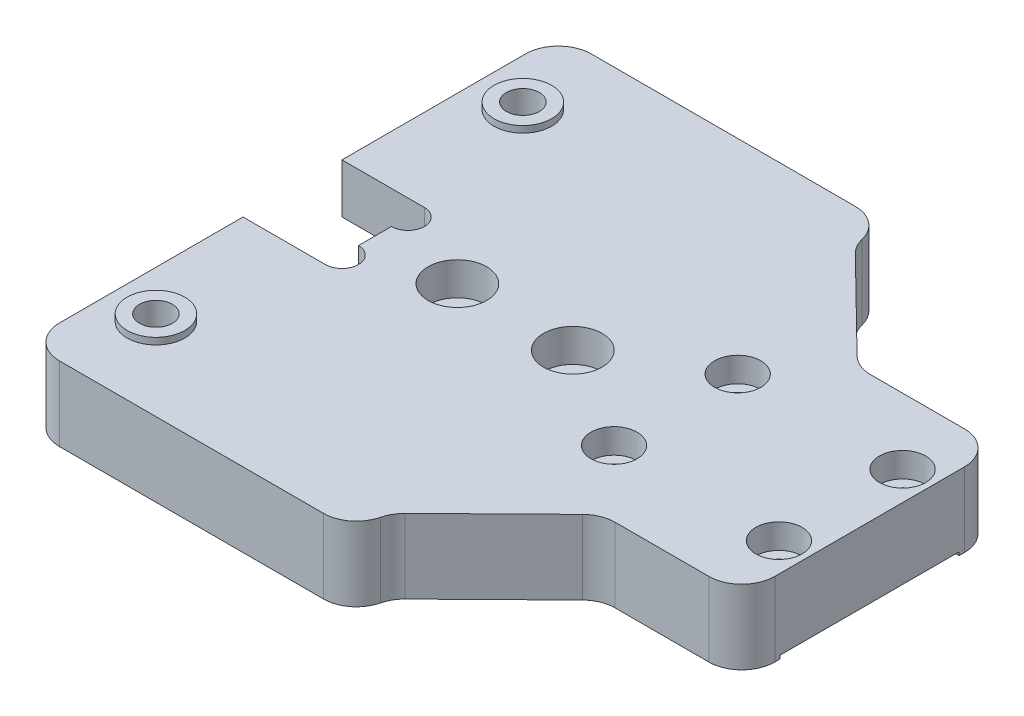
SolidWorks part; units mm, degrees
ref_plane "Front Plane" through (0, 0, 0) normal (0, 0, 1) x (1, 0, 0)
ref_plane "Top Plane" through (0, 0, 0) normal (0, 1, 0) x (1, 0, 0)
ref_plane "Right Plane" through (0, 0, 0) normal (1, 0, 0) x (0, 0, -1)
sketch "Sketch1" plane through (0, 0, 0) normal (0, 1, 0) x (1, 0, 0)
  line L0 (0, 0) -> (21.5, 0) construction
  line L5 (21.5, 20) -> (21.5, -20)
  line L6 (21.5, -20) -> (-20.5, -32.5)
  line L7 (-20.5, -32.5) -> (-84.5, -32.5)
  line L8 (-84.5, -32.5) -> (-84.5, 32.5)
  line L11 (-84.5, 32.5) -> (-20.5, 32.5)
  line L12 (-20.5, 32.5) -> (21.5, 20)
  circle A0 centre (0, 0) radius 12
  point P7 (21.5, 0)
  dimension "D4" = 24
  dimension "D6" = 9.5
  dimension "D1" = 40
  dimension "D2" = 106
  dimension "D3" = 65
  dimension "D5" = 64
extrude "Boss-Extrude1" add sketch "Sketch1" along normal mid plane 9
sketch "Sketch2" plane through (0, 4.5, 0) normal (0, 1, 0) x (1, 0, 0)
  line L0 (0, 0) -> (-19.5, 0) construction
  line L1 (-15.5, -15.5) -> (15.5, -15.5) construction
  line L2 (-15.5, -15.5) -> (-15.5, 15.5) construction
  line L3 (-15.5, 15.5) -> (15.5, 15.5) construction
  line L4 (15.5, -15.5) -> (15.5, 15.5) construction
  line L5 (-15.5, -15.5) -> (15.5, 15.5) construction
  line L6 (-15.5, 15.5) -> (15.5, -15.5) construction
  line L7 (-19.5, 27.5) -> (-19.5, -27.5) construction
  line L9 (-84.5, 32.5) -> (-84.5, -32.5) construction
  circle A0 centre (15.5, 15.5) radius 1.7
  circle A1 centre (-15.5, 15.5) radius 1.7
  circle A2 centre (-15.5, -15.5) radius 1.7
  circle A3 centre (15.5, -15.5) radius 1.7
  circle A4 centre (-19.5, 27.5) radius 1.7
  circle A5 centre (-19.5, -27.5) radius 1.7
  point P0 (0, 0)
  dimension "D2" = 3.4
  dimension "D1" = 31
  dimension "D3" = 55
  dimension "D4" = 65
extrude "Cut-Extrude1" cut sketch "Sketch2" against normal through all
fillet "Fillet1" radius 4 6 edges at (-84.5, 0, -32.5) (-84.5, 0, 32.5) (-20.5, 0, 32.5) (21.5, 0, 20) (-20.5, 0, -32.5) (21.5, 0, -20)
sketch "Sketch5" plane through (0, 4.5, 0) normal (0, 1, 0) x (1, 0, 0)
  line L0 (-24.5, 32.5) -> (-24.5, 10)
  line L1 (-21.0826, 32.5) -> (-80.5, 32.5) construction
  line L2 (-80.5, -32.5) -> (-21.0826, -32.5) construction
  line L3 (-84.5, 28.5) -> (-84.5, -28.5) construction
  line L4 (-24.5, 32.5) -> (26.912, 32.5)
  line L5 (-24.5, -10) -> (-29.5, -10) construction
  line L6 (-24.5, -10) -> (-24.5, 10) construction
  line L7 (-24.5, 10) -> (-29.5, 10) construction
  line L8 (-29.5, -10) -> (-29.5, 10) construction
  line L9 (26.912, 32.5) -> (26.912, -32.5)
  line L11 (-24.5, -32.5) -> (26.912, -32.5)
  line L12 (-24.5, 10) -> (-24.5, -10) construction
  line L13 (-24.5, -10) -> (-24.5, -32.5)
  line L14 (-29.5, 0) -> (0, 0) construction
  line L15 (-24.5, 10) -> (-24.5, -10)
  dimension "D1" = 60
  dimension "D2" = 20
  dimension "D3" = 5
extrude "Cut-Extrude4" cut sketch "Sketch5" against normal through all
fillet "Fillet3" radius 4 2 edges at (-24.5, 0, -32.5) (-24.5, 0, 32.5)
sketch "Sketch6" plane through (0, -4.5, 0) normal (0, -1, 0) x (1, 0, 0)
  line L0 (-48, -7.5) -> (-48, 7.5) construction
  line L3 (-48, -7.5) -> (-28, -7.5) construction
  line L4 (-28, -7.5) -> (-28, 7.5) construction
  line L5 (-28, 7.5) -> (-48, 7.5) construction
  line L6 (-24.5, -28.5) -> (-24.5, 28.5) construction
  line L7 (-28.5, -32.5) -> (-80.5, -32.5) construction
  circle A0 centre (-48, -7.5) radius 1.5
  circle A1 centre (-48, 7.5) radius 1.5
  circle A2 centre (-28, 7.5) radius 1.5
  circle A3 centre (-28, -7.5) radius 1.5
  dimension "D3" = 3.5
  dimension "D5" = 3
  dimension "D1" = 15
  dimension "D2" = 20
  dimension "D4" = 25
extrude "Cut-Extrude5" cut sketch "Sketch6" against normal blind 41
sketch "Sketch7" plane through (0, 4.5, 0) normal (0, 1, 0) x (1, 0, 0)
  line L0 (-84.5, 28.5) -> (-84.5, -28.5) construction
  line L1 (-84.5, 10) -> (-54.5, 10)
  line L2 (-84.5, 10) -> (-84.5, -10)
  line L3 (-84.5, -10) -> (-54.5, -10)
  line L4 (-54.5, 10) -> (-54.5, -10)
  line L5 (-28.5, 32.5) -> (-80.5, 32.5) construction
  dimension "D1" = 20
  dimension "D2" = 22.5
  dimension "D3" = 30
extrude "Cut-Extrude6" cut sketch "Sketch7" against normal blind 3 from offset 6 offset against normal yes
sketch "Sketch8" plane through (0, 4.5, 0) normal (0, 1, 0) x (1, 0, 0)
  line L0 (-84.5, 28.5) -> (-84.5, -28.5) construction
  line L1 (-84.5, 15.5) -> (-24.5, 15.5)
  line L2 (-84.5, 15.5) -> (-84.5, 32.5)
  line L3 (-84.5, 32.5) -> (-24.5, 32.5)
  line L4 (-24.5, 15.5) -> (-24.5, 32.5)
  line L5 (-84.5, 28.5) -> (-84.5, -28.5) construction
  line L7 (-24.5, 28.5) -> (-24.5, -28.5) construction
  line L8 (-28.5, 32.5) -> (-80.5, 32.5) construction
  line L9 (-84.5, 0) -> (-24.5, 0) construction
  line L11 (-84.5, -32.5) -> (-24.5, -32.5)
  line L12 (-24.5, -15.5) -> (-24.5, -32.5)
  line L13 (-84.5, -15.5) -> (-24.5, -15.5)
  line L14 (-84.5, -15.5) -> (-84.5, -32.5)
  dimension "D1" = 17
extrude "Cut-Extrude8" cut sketch "Sketch8" against normal blind 9
fillet "Fillet6" radius 4 2 edges at (-24.5, 0, -15.5) (-24.5, 0, 15.5)
sketch "Sketch9" plane through (0, 4.5, 0) normal (0, 1, 0) x (1, 0, 0)
  line L0 (-84.5, 15.5) -> (-28.5, 15.5) construction
  line L1 (-54.5, 10) -> (-94.5, 10)
  line L2 (-54.5, 10) -> (-54.5, 32.25)
  line L3 (-54.5, 32.25) -> (-94.5, 32.25)
  line L4 (-94.5, 10) -> (-94.5, 32.25)
  line L5 (-24.5, 11.5) -> (-24.5, -11.5) construction
  line L7 (-24.5, 0) -> (-84.5, 0) construction
  line L9 (-54.5, -32.25) -> (-94.5, -32.25)
  line L10 (-94.5, -10) -> (-94.5, -32.25)
  line L11 (-54.5, -10) -> (-94.5, -10)
  line L12 (-54.5, -10) -> (-54.5, -32.25)
  line L13 (-84.5, 15.5) -> (-84.5, -15.5) construction
  dimension "D1" = 30
  dimension "D2" = 40
  dimension "D3" = 22.25
  dimension "D4" = 5.5
extrude "Boss-Extrude3" add sketch "Sketch9" against normal blind 9
fillet "Fillet7" radius 4 4 edges at (-94.5, 0, -32.25) (-54.5, 0, -32.25) (-54.5, 0, 32.25) (-94.5, 0, 32.25)
sketch "Sketch13" plane through (0, 4.5, 0) normal (0, 1, 0) x (1, 0, 0)
  line L0 (-84.5, 0) -> (-24.5, 0) construction
  line L1 (-84.5, 10) -> (-84.5, -10) construction
  line L2 (-24.5, 11.5) -> (-24.5, -11.5) construction
  line L3 (-58.5, 32.25) -> (-90.5, 32.25) construction
  line L4 (-94.5, 28.25) -> (-94.5, 10) construction
  circle A0 centre (-88.81, 22.25) radius 3.5
  circle A1 centre (-88.81, -22.25) radius 3.5
  dimension "D1" = 7
  dimension "D2" = 10
  dimension "D3" = 5.69
extrude "Boss-Extrude5" add sketch "Sketch13" along normal blind 0.8
sketch "Sketch10" plane through (0, 4.5, 0) normal (0, 1, 0) x (1, 0, 0)
  line L0 (-94.5, -10) -> (-94.5, -28.25) construction
  line L1 (-90.5, -32.25) -> (-58.5, -32.25) construction
  line L2 (-24.5, 0) -> (-84.5, 0) construction
  line L3 (-24.5, 11.5) -> (-24.5, -11.5) construction
  line L4 (-84.5, 10) -> (-84.5, -10) construction
  circle A0 centre (-88.81, -22.25) radius 2
  circle A1 centre (-88.81, 22.25) radius 2
  dimension "D2" = 10
  dimension "D3" = 4
  dimension "D1" = 5.69
extrude "Cut-Extrude9" cut sketch "Sketch10" against normal blind 9 and the other way blind 2
sketch "Sketch11" plane through (0, 4.5, 0) normal (0, 1, 0) x (1, 0, 0)
  line L0 (-54.5, 28.25) -> (-41.5, 15.5)
  line L1 (-54.5, 15.5) -> (-54.5, 28.25) construction
  line L2 (-54.5, 15.5) -> (-28.5, 15.5) construction
  line L3 (-54.5, -28.25) -> (-41.5, -15.5)
  line L4 (-28.5, -15.5) -> (-54.5, -15.5) construction
  line L5 (-54.5, -28.25) -> (-54.5, -15.5) construction
  line L6 (-54.5, 28.25) -> (-54.5, 15.5)
  line L7 (-54.5, 15.5) -> (-41.5, 15.5)
  line L8 (-54.5, -28.25) -> (-54.5, -15.5)
  line L9 (-54.5, -15.5) -> (-41.5, -15.5)
  arc A0 (-58.5, -32.25) -> (-54.5, -28.25) centre (-58.5, -28.25) ccw construction
  arc A1 (-54.5, 28.25) -> (-58.5, 32.25) centre (-58.5, 28.25) ccw construction
extrude "Boss-Extrude4" add sketch "Sketch11" against normal blind 9
sketch "Sketch14" plane through (0, -1.5, 0) normal (0, -1, 0) x (1, 0, 0)
  line L0 (-84.5, 0) -> (-24.5, 0) construction
  line L1 (-84.5, -10) -> (-84.5, 10) construction
  line L2 (-24.5, -11.5) -> (-24.5, 11.5) construction
  line L3 (-54.5, 10) -> (-54.5, -10) construction
  circle A0 centre (-74.5, 0) radius 2
  circle A1 centre (-60.5, 0) radius 2
  dimension "D1" = 4
  dimension "D2" = 4
  dimension "D3" = 6
  dimension "D4" = 14
extrude "Cut-Extrude10" cut sketch "Sketch14" against normal blind 16
sketch "Sketch15" plane through (0, -4.5, 0) normal (0, -1, 0) x (1, 0, 0)
  line L0 (-24.5, -11.5) -> (-24.5, 11.5) construction
  line L1 (-24.5, 10.85) -> (-32, 10.85)
  line L2 (-24.5, 10.85) -> (-24.5, -10.85)
  line L3 (-24.5, -10.85) -> (-32, -10.85)
  line L4 (-32, 10.85) -> (-32, -10.85)
  line L5 (-28.5, 15.5) -> (-41.5, 15.5) construction
  line L6 (-38, 15.5) -> (-38, -15.5) construction
  line L7 (-41.5, -15.5) -> (-28.5, -15.5) construction
  line L8 (-51.5, 10.85) -> (-44, 10.85)
  line L9 (-51.5, 10.85) -> (-51.5, -10.85)
  line L10 (-44, 10.85) -> (-44, -10.85)
  line L11 (-51.5, -10.85) -> (-44, -10.85)
  dimension "D1" = 7.5
  dimension "D2" = 21.7
  dimension "D3" = 4.65
  dimension "D4" = 13.5
extrude "Cut-Extrude11" cut sketch "Sketch15" against normal blind 0.4
chamfer "Chamfer2" distance 0.4 angle 45 2 edges at (-32, -4.1, 0) (-44, -4.1, 0)
chamfer "Chamfer3" distance 0.6 angle 45 1 edges at (-51.5, -4.1, 0)
sketch "Sketch16" plane through (-84.5, 0, 0) normal (-1, 0, 0) x (0, 0, 1)
  line L0 (-10, 4.5) -> (10, 4.5) construction
  line L1 (-10, 4.5) -> (-6, 4.5)
  line L2 (-10, 4.5) -> (-10, -1.5)
  line L3 (-10, -1.5) -> (-6, -1.5)
  line L4 (-6, 4.5) -> (-6, -1.5)
  line L5 (-10, 4.5) -> (-10, -1.5) construction
  line L6 (-10, -1.5) -> (10, -1.5) construction
  line L8 (10, 4.5) -> (6, 4.5)
  line L9 (10, 4.5) -> (10, -1.5)
  line L10 (10, -1.5) -> (6, -1.5)
  line L11 (6, 4.5) -> (6, -1.5)
  line L12 (10, -1.5) -> (10, 4.5) construction
  dimension "D1" = 4
extrude "Boss-Extrude6" add sketch "Sketch16" along normal blind 10
sketch "Sketch17" plane through (0, 4.5, 0) normal (0, 1, 0) x (1, 0, 0)
  line L0 (-84.5, 0) -> (-24.5, 0) construction
  line L1 (-84.5, 6) -> (-84.5, -6) construction
  line L2 (-24.5, 11.5) -> (-24.5, -11.5) construction
  line L3 (-94.5, 6) -> (-84.5, 6) construction
  circle A0 centre (-84.5, 4) radius 2
  circle A1 centre (-84.5, -4) radius 2
  dimension "D1" = 4
extrude "Cut-Extrude12" cut sketch "Sketch17" against normal blind 12.4
sketch "Sketch18" plane through (0, 4.5, 0) normal (0, 1, 0) x (1, 0, 0)
  line L0 (-60.5, 0) -> (-74.5, 0) construction
  line L1 (-90.5, -32.25) -> (-58.5, -32.25) construction
  line L2 (-84.5, 2) -> (-84.5, -2) construction
  circle A0 centre (-74.5, 0) radius 3.55
  circle A1 centre (-60.5, 0) radius 3.55
  dimension "D1" = 7.1
  dimension "D2" = 14
  dimension "D3" = 32.25
  dimension "D4" = 10
extrude "Cut-Extrude13" cut sketch "Sketch18" against normal blind 4
sketch "Sketch19" plane through (0, 4.5, 0) normal (0, 1, 0) x (1, 0, 0)
  line L0 (-48, 7.5) -> (-48, -7.5) construction
  line L1 (-48, -7.5) -> (-28, -7.5) construction
  line L2 (-28, -7.5) -> (-28, 7.5) construction
  line L3 (-28, 7.5) -> (-48, 7.5) construction
  line L4 (-41.5, 15.5) -> (-28.5, 15.5) construction
  line L5 (-24.5, 11.5) -> (-24.5, -11.5) construction
  circle A0 centre (-48, 7.5) radius 2.8
  circle A1 centre (-28, 7.5) radius 2.8
  circle A2 centre (-48, -7.5) radius 2.8
  circle A3 centre (-28, -7.5) radius 2.8
  dimension "D3" = 5.6
  dimension "D1" = 15
  dimension "D2" = 20
  dimension "D4" = 8
  dimension "D5" = 3.5
extrude "Cut-Extrude14" cut sketch "Sketch19" against normal blind 3
sketch "Sketch20" plane through (0, -4.5, 0) normal (0, -1, 0) x (1, 0, 0)
  line L0 (-32, 10.85) -> (-32, -10.85) construction
  line L1 (-24.5, 10.85) -> (-32, 10.85) construction
  line L2 (-31.6, -10.85) -> (-24.5, -10.85) construction
  line L3 (-51.3, -10.85) -> (-51.3, 10.85) construction
  line L4 (-44, -10.85) -> (-44, 10.85) construction
  line L5 (-44, 10.85) -> (-51.3, 10.85) construction
  line L6 (-51.3, -10.85) -> (-44, -10.85) construction
  line L11 (-50.9, 10.85) -> (-50.9, -10.85) construction
  line L12 (-51.3, -6.85) -> (-50.9, -6.85)
  line L14 (-51.3, -10.85) -> (-50.9, -10.85)
  line L15 (-50.9, -6.85) -> (-50.9, -10.85)
  line L16 (-44.4, -10.85) -> (-44.4, 10.85) construction
  line L17 (-44, -6.85) -> (-44.4, -6.85)
  line L19 (-44, -10.85) -> (-44.4, -10.85)
  line L20 (-44.4, -6.85) -> (-44.4, -10.85)
  line L22 (-51.3, 6.85) -> (-50.9, 6.85)
  line L24 (-51.3, 10.85) -> (-50.9, 10.85)
  line L25 (-50.9, 6.85) -> (-50.9, 10.85)
  line L26 (-44, 6.85) -> (-44.4, 6.85)
  line L28 (-44, 10.85) -> (-44.4, 10.85)
  line L29 (-44.4, 6.85) -> (-44.4, 10.85)
  circle A0 centre (-32, 8.85) radius 2
  circle A1 centre (-32, -8.85) radius 2
  arc A2 (-51.3, 10.85) -> (-51.3, 6.85) centre (-51.3, 8.85) ccw
  arc A3 (-51.3, -6.85) -> (-51.3, -10.85) centre (-51.3, -8.85) ccw
  arc A4 (-44, -10.85) -> (-44, -6.85) centre (-44, -8.85) ccw
  arc A5 (-44, 6.85) -> (-44, 10.85) centre (-44, 8.85) ccw
  dimension "D1" = 4
extrude "Cut-Extrude15" cut sketch "Sketch20" against normal blind 0.4
fillet "Fillet8" radius 4 4 edges at (-54.5, 0, -28.25) (-41.5, 0, -15.5) (-41.5, 0, 15.5) (-54.5, 0, 28.25)
sketch "Sketch21" plane through (0, -4.5, 0) normal (0, -1, 0) x (1, 0, 0)
  line L0 (-94.5, 10) -> (-54.5, 10) construction
  line L1 (-54.5, 10) -> (-54.5, -10) construction
  line L2 (-54.5, -10) -> (-94.5, -10) construction
  line L3 (-54.5, 10) -> (-54.5, -10) construction
  circle A0 centre (-56.5, 10) radius 2
  circle A1 centre (-56.5, -10) radius 2
  dimension "D1" = 4
extrude "Cut-Extrude16" cut sketch "Sketch21" against normal blind 3
